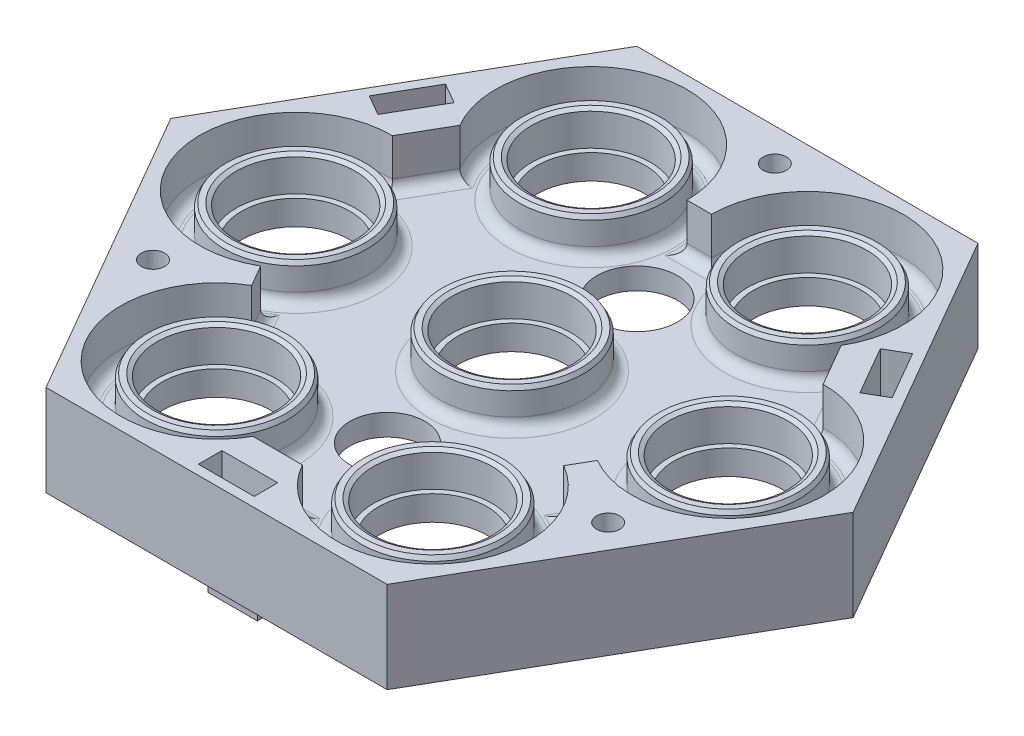
SolidWorks part; units mm, degrees
note: The reader was unsure of these and kept them because the rebuilt part matched: shared geometry of "Sketch3<3>", "Sketch3<4>".
material "PLA"
ref_plane "Front Plane" through (0, 0, 0) normal (0, 0, 1) x (1, 0, 0)
ref_plane "Top Plane" through (0, 0, 0) normal (0, 1, 0) x (1, 0, 0)
ref_plane "Right Plane" through (0, 0, 0) normal (1, 0, 0) x (0, 0, -1)
sketch "Sketch1" plane through (0, 0, 0) normal (0, 1, 0) x (1, 0, 0)
  line L0 (-63.5653, 0) -> (-31.7827, -55.0492)
  line L1 (-29.0764, -19.4379) -> (-31.3719, -15.4619)
  line L2 (-63.5653, 0) -> (-58.1527, 0)
  line L3 (-4.5986, -43.671) -> (4.5986, -43.671)
  line L4 (31.7827, -55.0492) -> (29.0764, -50.3617)
  line L5 (-31.7827, -55.0492) -> (31.7827, -55.0492)
  line L6 (31.7827, 55.0492) -> (-31.7827, 55.0492)
  line L7 (-2.2955, 34.8998) -> (2.2955, 34.8998)
  line L8 (31.7827, 55.0492) -> (29.0764, 50.3617)
  line L9 (-35.5209, 25.818) -> (-40.1195, 17.853)
  line L10 (-63.5653, 0) -> (-58.1527, 0)
  line L11 (-31.7827, 55.0492) -> (-63.5653, 0)
  line L12 (31.7827, -55.0492) -> (63.5653, 0)
  line L13 (31.3719, -15.4619) -> (29.0764, -19.4379)
  line L14 (31.7827, -55.0492) -> (29.0764, -50.3617)
  line L15 (40.1195, 17.853) -> (35.5209, 25.818)
  line L16 (31.7827, 55.0492) -> (29.0764, 50.3617)
  line L17 (63.5653, 0) -> (31.7827, 55.0492)
  arc A0 (-31.3719, -15.4619) -> (-58.1527, 0) centre (-40.2988, 0) cw
  arc A1 (-4.5986, -43.671) -> (-29.0764, -19.4379) centre (-20.1494, -34.8998) cw
  arc A2 (4.5986, -43.671) -> (29.0764, -50.3617) centre (20.1494, -34.8998) ccw
  arc A3 (2.2955, 34.8998) -> (29.0764, 50.3617) centre (20.1494, 34.8998) cw
  arc A4 (-35.5209, 25.818) -> (-2.2955, 34.8998) centre (-20.1494, 34.8998) cw
  arc A5 (-40.1195, 17.853) -> (-58.1527, 0) centre (-40.2988, 0) ccw
  arc A6 (29.0764, -19.4379) -> (29.0764, -50.3617) centre (20.1494, -34.8998) cw
  arc A7 (40.1195, 17.853) -> (31.3719, -15.4619) centre (40.2988, 0) cw
  arc A8 (35.5209, 25.818) -> (29.0764, 50.3617) centre (20.1494, 34.8998) ccw
  point P36 (0, 0)
extrude "Boss-Extrude1" add sketch "Sketch1" against normal blind 28.05 contours A2 L3 A1 L1 A0 L2 L0 L5 L4 | A5 L9 A4 L7 A3 L8 L6 L11 L2 | A8 L15 A7 L13 A6 L4 L12 L17 L8
ref_plane "Plane1" through (0, -20.046, 0) normal (0, 1, 0) x (1, 0, 0)
sketch "Sketch3" plane through (0, -20.046, 0) normal (0, 1, 0) x (1, 0, 0)
  line L0 (-29.0764, -19.4379) -> (-31.3719, -15.4619) construction
  line L1 (-4.5986, -43.671) -> (4.5986, -43.671) construction
  line L2 (31.3719, -15.4619) -> (29.0764, -19.4379) construction
  line L3 (40.1195, 17.853) -> (35.5209, 25.818) construction
  line L4 (-2.2955, 34.8998) -> (2.2955, 34.8998) construction
  line L5 (-35.5209, 25.818) -> (-40.1195, 17.853) construction
  line L6 (-29.0764, -19.4379) -> (-31.3719, -15.4619)
  line L7 (-4.5986, -43.671) -> (4.5986, -43.671)
  line L8 (31.3719, -15.4619) -> (29.0764, -19.4379)
  line L9 (40.1195, 17.853) -> (35.5209, 25.818)
  line L10 (-2.2955, 34.8998) -> (2.2955, 34.8998)
  line L11 (-35.5209, 25.818) -> (-40.1195, 17.853)
  circle A0 centre (-20.1494, 34.8998) radius 11.1
  circle A1 centre (0, 0) radius 11.1
  circle A2 centre (-20.1494, 34.8998) radius 13.35
  circle A3 centre (0, 0) radius 13.35
  circle A4 centre (-20.1494, 34.8998) radius 10.1
  circle A5 centre (0, 0) radius 10.1
  circle A6 centre (20.1494, 34.8998) radius 13.35
  circle A7 centre (20.1494, 34.8998) radius 11.1
  circle A8 centre (20.1494, 34.8998) radius 10.1
  circle A9 centre (40.2988, 0) radius 13.35
  circle A10 centre (40.2988, 0) radius 11.1
  circle A11 centre (40.2988, 0) radius 10.1
  circle A12 centre (20.1494, -34.8998) radius 13.35
  circle A13 centre (20.1494, -34.8998) radius 11.1
  circle A14 centre (20.1494, -34.8998) radius 10.1
  circle A15 centre (-20.1494, -34.8998) radius 13.35
  circle A16 centre (-20.1494, -34.8998) radius 11.1
  circle A17 centre (-20.1494, -34.8998) radius 10.1
  circle A18 centre (-40.2988, 0) radius 13.35
  circle A19 centre (-40.2988, 0) radius 11.1
  circle A20 centre (-40.2988, 0) radius 10.1
  arc A21 (-40.1195, 17.853) -> (-31.3719, -15.4619) centre (-40.2988, 0) ccw construction
  arc A22 (-29.0764, -19.4379) -> (-4.5986, -43.671) centre (-20.1494, -34.8998) ccw construction
  arc A23 (4.5986, -43.671) -> (29.0764, -19.4379) centre (20.1494, -34.8998) ccw construction
  arc A24 (31.3719, -15.4619) -> (40.1195, 17.853) centre (40.2988, 0) ccw construction
  arc A25 (35.5209, 25.818) -> (2.2955, 34.8998) centre (20.1494, 34.8998) ccw construction
  arc A26 (-2.2955, 34.8998) -> (-35.5209, 25.818) centre (-20.1494, 34.8998) ccw construction
  arc A27 (-40.1195, 17.853) -> (-31.3719, -15.4619) centre (-40.2988, 0) ccw
  arc A28 (-29.0764, -19.4379) -> (-4.5986, -43.671) centre (-20.1494, -34.8998) ccw
  arc A29 (4.5986, -43.671) -> (29.0764, -19.4379) centre (20.1494, -34.8998) ccw
  arc A30 (31.3719, -15.4619) -> (40.1195, 17.853) centre (40.2988, 0) ccw
  arc A31 (35.5209, 25.818) -> (2.2955, 34.8998) centre (20.1494, 34.8998) ccw
  arc A32 (-2.2955, 34.8998) -> (-35.5209, 25.818) centre (-20.1494, 34.8998) ccw
  circle A33 centre (0, 0) radius 6.25
  circle A34 centre (-40.2988, 0) radius 6.25
  circle A35 centre (-20.1494, 34.8998) radius 6.25
  circle A36 centre (20.1494, 34.8998) radius 6.25
  circle A37 centre (40.2988, 0) radius 6.25
  circle A38 centre (20.1494, -34.8998) radius 6.25
  circle A39 centre (-20.1494, -34.8998) radius 6.25
  point P46 (0, 0)
  point P71 (0, 0)
  dimension "D1" = 22.2
  dimension "D2" = 22.2
  dimension "D8" = 12.5
  dimension "D9" = 12.5
  dimension "D3" = 2.25
  dimension "D4" = 2.25
  dimension "D5" = 1
  dimension "D6" = 1
  dimension "D7" = 6
  dimension "D10" = 6
extrude "Boss-Extrude2" add sketch "Sketch3" against normal offset from surface (2.494 mm away) 4 contours L10 A32 L11 A27 L6 A28 L7 A29 L8 A30 L9 A31 A2 A3 A6 A9 A12 A15 A18 | A18 A19 | A19 A20 | A20 | A5 | A3 A1 | A1 A5 | A4 | A0 A4 | A2 A0 | A8 | A7 A8 | A6 A7 | A11 | A10 A11 | A9 A10 | A14 | A13 A14 | A12 A13 | A17 | A16 A17 | A15 A16
extrude "Boss-Extrude3" add sketch "Sketch3<3>" along normal blind 0.6 contours A1 A5 | A19 A20 | A0 A4 | A16 A17 | A13 A14 | A7 A8 | A10 A11
sketch "Sketch3<3>" plane through (0, -20.046, 0) normal (0, 1, 0) x (1, 0, 0) same geometry as "Sketch3"
extrude "Boss-Extrude4" add sketch "Sketch3<4>" along normal blind 7 contours A18 A19 | A3 A1 | A2 A0 | A15 A16 | A9 A10 | A12 A13 | A6 A7
sketch "Sketch3<4>" plane through (0, -20.046, 0) normal (0, 1, 0) x (1, 0, 0) same geometry as "Sketch3"
chamfer "Chamfer1" distance 0.75 angle 30 14 edges at (-20.1494, -13.046, -21.5498) (-20.1494, -13.046, -23.7998) (20.1494, -13.046, -23.7998) (20.1494, -13.046, -21.5498) (40.2988, -13.046, 11.1) (40.2988, -13.046, 13.35) (20.1494, -13.046, 48.2498) (20.1494, -13.046, 45.9998) (-20.1494, -13.046, 45.9998) (-20.1494, -13.046, 48.2498) (0, -13.046, 13.35) (0, -13.046, 11.1) (-40.2988, -13.046, 13.35) (-40.2988, -13.046, 11.1)
sketch "Sketch4" plane through (0, -28.05, 0) normal (0, -1, 0) x (1, 0, 0)
  line L0 (-47.674, -27.5246) -> (47.674, 27.5246) construction
  line L1 (-31.7827, -55.0492) -> (-63.5653, 0) construction
  line L2 (31.7827, 55.0492) -> (63.5653, 0) construction
  line L3 (-47.3762, -22.0405) -> (-42.7757, -30.0087)
  line L4 (-47.3762, -22.0405) -> (-44.7781, -20.5405)
  line L5 (-42.7757, -30.0087) -> (-40.1776, -28.5087)
  line L6 (-44.7781, -20.5405) -> (-40.1776, -28.5087)
  line L7 (4.6005, 52.0492) -> (-4.6005, 52.0492)
  line L8 (4.6005, 52.0492) -> (4.6005, 49.0492)
  line L9 (4.6005, 49.0492) -> (-4.6005, 49.0492)
  line L10 (-4.6005, 52.0492) -> (-4.6005, 49.0492)
  line L11 (42.7757, -30.0087) -> (47.3762, -22.0405)
  line L12 (42.7757, -30.0087) -> (40.1776, -28.5087)
  line L13 (40.1776, -28.5087) -> (44.7781, -20.5405)
  line L14 (47.3762, -22.0405) -> (44.7781, -20.5405)
  point P6 (-42.4778, -24.5246)
  point P21 (0, 0)
  dimension "D1" = 3
  dimension "D2" = 3
  dimension "D3" = 3
extrude "Boss-Extrude5" add sketch "Sketch4" along normal blind 4
sketch "Sketch5" plane through (0, 0, 0) normal (0, 1, 0) x (1, 0, 0)
  line L0 (-63.5653, 0) -> (-31.7827, -55.0492) construction
  line L1 (-30.2241, -17.4499) -> (-47.674, -27.5246) construction
  line L2 (-29.0764, -19.4379) -> (-31.3719, -15.4619) construction
  circle A0 centre (-42.4086, -24.4846) radius 2.175
  circle A1 centre (0, 48.9692) radius 2.175
  circle A2 centre (42.4086, -24.4846) radius 2.175
  point P14 (0, 0)
  dimension "D2" = 4.35
  dimension "D1" = 6.08
  dimension "D3" = 3
extrude "Cut-Extrude1" cut sketch "Sketch5" against normal blind 16.25
sketch "Sketch6" plane through (0, -20.046, 0) normal (0, 1, 0) x (1, 0, 0)
  line L0 (0, 55.0492) -> (0, -55.0492) construction
  line L1 (31.7827, 55.0492) -> (-31.7827, 55.0492) construction
  line L2 (-31.7827, -55.0492) -> (31.7827, -55.0492) construction
  circle A0 centre (0, 23.3222) radius 7.5
  circle A1 centre (0, -23.2122) radius 7
  dimension "D3" = 15
  dimension "D4" = 14
  dimension "D1" = 31.727
  dimension "D2" = 31.837
fillet "Fillet2" radius 2 19 edges at (40.2988, -20.046, 13.35) (-20.1494, -20.046, 48.2498) (-20.1494, -20.046, -21.5498) (0, -20.046, 13.35) (20.1494, -20.046, 48.2498) (20.1494, -20.046, -21.5498) (-40.2988, -20.046, 13.35) (-30.2241, -20.046, 17.4499) (30.2241, -20.046, 17.4499) (0, -20.046, -34.8998) (-24.8569, -20.046, -52.1219) (-37.8202, -20.046, -21.8355) (-57.5673, -20.046, 4.5343) (-32.7105, -20.046, 47.5877) (0, -20.046, 43.671) (32.7105, -20.046, 47.5877) (57.5673, -20.046, 4.5343) (37.8202, -20.046, -21.8355) (24.8569, -20.046, -52.1219)
fillet "Fillet3" radius 2 12 edges at (37.8202, -24.05, -21.8355) (30.2241, -24.05, 17.4499) (32.7105, -24.05, 47.5877) (0, -24.05, 43.671) (57.5673, -24.05, 4.5343) (-30.2241, -24.05, 17.4499) (-32.7105, -24.05, 47.5877) (24.8569, -24.05, -52.1219) (0, -24.05, -34.8998) (-24.8569, -24.05, -52.1219) (-37.8202, -24.05, -21.8355) (-57.5673, -24.05, 4.5343)
extrude "Cut-Extrude2" cut sketch "Sketch6" against normal through all contours A1 L0 | L0 A1 | L0 A0 | A0 L0
sketch "Sketch7" plane through (0, 0, 0) normal (0, 1, 0) x (1, 0, 0)
  line L0 (-63.5653, 0) -> (-31.7827, 55.0492)
  line L1 (-31.7827, 55.0492) -> (31.7827, 55.0492)
  line L2 (31.7827, 55.0492) -> (63.5653, 0)
  line L3 (63.5653, 0) -> (31.7827, -55.0492)
  line L4 (31.7827, -55.0492) -> (-31.7827, -55.0492)
  line L5 (-31.7827, -55.0492) -> (-63.5653, 0)
  line L6 (-2.2955, 34.8998) -> (2.2955, 34.8998) construction
  line L7 (35.5209, 25.818) -> (40.1195, 17.853) construction
  line L8 (-4.5986, -43.671) -> (4.5986, -43.671) construction
  line L9 (31.3719, -15.4619) -> (29.0764, -19.4379) construction
  line L10 (-40.1195, 17.853) -> (-35.5209, 25.818) construction
  line L11 (-29.0764, -19.4379) -> (-31.3719, -15.4619) construction
  line L12 (-2.2955, 34.8998) -> (2.2955, 34.8998)
  line L13 (35.5209, 25.818) -> (40.1195, 17.853)
  line L14 (-4.5986, -43.671) -> (4.5986, -43.671)
  line L15 (31.3719, -15.4619) -> (29.0764, -19.4379)
  line L16 (-40.1195, 17.853) -> (-35.5209, 25.818)
  line L17 (-29.0764, -19.4379) -> (-31.3719, -15.4619)
  circle A0 centre (42.4086, -24.4846) radius 2.175 construction
  circle A1 centre (0, 48.9692) radius 2.175 construction
  circle A2 centre (-42.4086, -24.4846) radius 2.175 construction
  circle A3 centre (42.4086, -24.4846) radius 2.175
  circle A4 centre (0, 48.9692) radius 2.175
  circle A5 centre (-42.4086, -24.4846) radius 2.175
  arc A6 (35.5209, 25.818) -> (2.2955, 34.8998) centre (20.1494, 34.8998) ccw construction
  arc A7 (-2.2955, 34.8998) -> (-35.5209, 25.818) centre (-20.1494, 34.8998) ccw construction
  arc A8 (31.3719, -15.4619) -> (40.1195, 17.853) centre (40.2988, 0) ccw construction
  arc A9 (4.5986, -43.671) -> (29.0764, -19.4379) centre (20.1494, -34.8998) ccw construction
  arc A10 (-29.0764, -19.4379) -> (-4.5986, -43.671) centre (-20.1494, -34.8998) ccw construction
  arc A11 (-40.1195, 17.853) -> (-31.3719, -15.4619) centre (-40.2988, 0) ccw construction
  arc A12 (35.5209, 25.818) -> (2.2955, 34.8998) centre (20.1494, 34.8998) ccw
  arc A13 (-2.2955, 34.8998) -> (-35.5209, 25.818) centre (-20.1494, 34.8998) ccw
  arc A14 (31.3719, -15.4619) -> (40.1195, 17.853) centre (40.2988, 0) ccw
  arc A15 (4.5986, -43.671) -> (29.0764, -19.4379) centre (20.1494, -34.8998) ccw
  arc A16 (-29.0764, -19.4379) -> (-4.5986, -43.671) centre (-20.1494, -34.8998) ccw
  arc A17 (-40.1195, 17.853) -> (-31.3719, -15.4619) centre (-40.2988, 0) ccw
extrude "Cut-Extrude3" cut sketch "Sketch7" against normal blind 11.05
sketch "Sketch8" plane through (0, -11.05, 0) normal (0, 1, 0) x (1, 0, 0)
  line L0 (-5, -49.0492) -> (-5, -53.0492) construction
  line L1 (-5, -49.0492) -> (5, -49.0492) construction
  line L2 (-5, -53.0492) -> (5, -53.0492) construction
  line L3 (5, -49.0492) -> (5, -53.0492) construction
  line L4 (0, 0) -> (0, -55.0492) construction
  line L5 (-31.7827, -55.0492) -> (31.7827, -55.0492) construction
  line L6 (0, -49.0492) -> (0, -53.0492) construction
  line L7 (-5.2, -48.8492) -> (-5.2, -53.2492)
  line L8 (-5.2, -53.2492) -> (5.2, -53.2492)
  line L9 (5.2, -48.8492) -> (5.2, -53.2492)
  line L10 (-5.2, -48.8492) -> (5.2, -48.8492)
  line L11 (-39.7046, 28.9279) -> (-43.5152, 31.1279)
  line L12 (-43.5152, 31.1279) -> (-48.7152, 22.1213)
  line L13 (-44.9046, 19.9213) -> (-48.7152, 22.1213)
  line L14 (-39.7046, 28.9279) -> (-44.9046, 19.9213)
  line L15 (44.9046, 19.9213) -> (48.7152, 22.1213)
  line L16 (48.7152, 22.1213) -> (43.5152, 31.1279)
  line L17 (39.7046, 28.9279) -> (43.5152, 31.1279)
  line L18 (44.9046, 19.9213) -> (39.7046, 28.9279)
  point P26 (0, 0)
  dimension "D1" = 2
  dimension "D2" = 4
  dimension "D3" = 10
  dimension "D4" = 0.2
  dimension "D5" = 3
extrude "Cut-Extrude4" cut sketch "Sketch8" against normal blind 11
equation "\"height_diff_support_plate_og_bushing\"=11.05"
equation "\"D1@Cut-Extrude3\"=\"height_diff_support_plate_og_bushing\""
equation "\"D1@Cut-Extrude1\"= 5.2 + \"height_diff_support_plate_og_bushing\""
